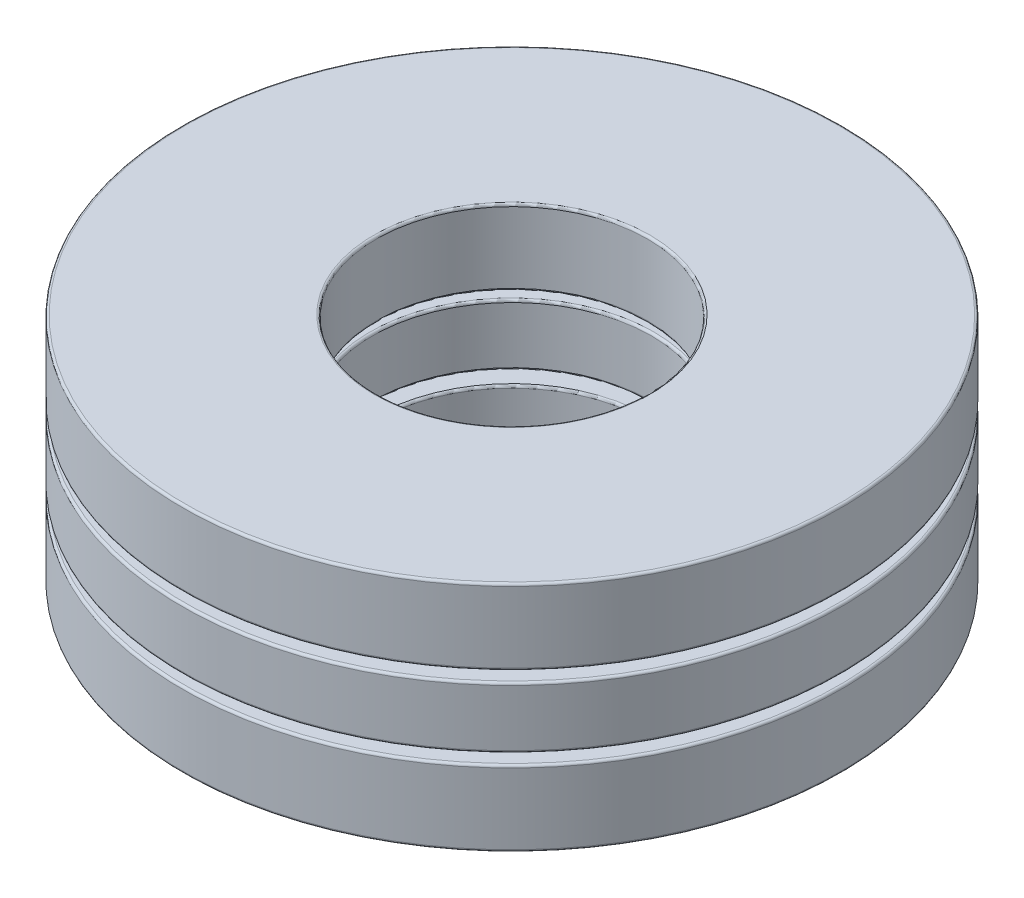
SolidWorks part; units mm, degrees
ref_plane "Front Plane" through (0, 0, 0) normal (0, 0, 1) x (1, 0, 0)
ref_plane "Top Plane" through (0, 0, 0) normal (0, 1, 0) x (1, 0, 0)
ref_plane "Right Plane" through (0, 0, 0) normal (1, 0, 0) x (0, 0, -1)
sketch "Sketch1" plane through (0, 0, 0) normal (0, 0, 1) x (1, 0, 0)
  line L0 (-8.5, 0.7275) -> (-8.5, -0.7275)
  line L1 (-8.44, -0.7875) -> (-3.66, -0.7875)
  line L2 (-3.6, -0.7275) -> (-3.6, 0.7275)
  line L3 (-3.66, 0.7875) -> (-8.44, 0.7875)
  line L4 (0, -3) -> (0, 3) construction
  line L5 (-8.5, 2.94) -> (-8.5, 1.115)
  line L6 (-8.44, 1.055) -> (-3.56, 1.055)
  line L7 (-3.5, 1.115) -> (-3.5, 2.94)
  line L8 (-3.56, 3) -> (-8.44, 3)
  line L9 (-6.375, 1.3225) -> (-6.375, 0.7875) construction
  arc A0 (-8.5, 0.7275) -> (-8.44, 0.7875) centre (-8.44, 0.7275) cw
  arc A1 (-3.66, 0.7875) -> (-3.6, 0.7275) centre (-3.66, 0.7275) cw
  arc A2 (-3.6, -0.7275) -> (-3.66, -0.7875) centre (-3.66, -0.7275) cw
  arc A3 (-8.44, -0.7875) -> (-8.5, -0.7275) centre (-8.44, -0.7275) cw
  circle A4 centre (-6.375, 0) radius 1.26
  arc A5 (-3.56, 1.055) -> (-3.5, 1.115) centre (-3.56, 1.115) ccw
  arc A6 (-3.5, 2.94) -> (-3.56, 3) centre (-3.56, 2.94) ccw
  arc A7 (-8.44, 3) -> (-8.5, 2.94) centre (-8.44, 2.94) ccw
  arc A8 (-8.5, 1.115) -> (-8.44, 1.055) centre (-8.44, 1.115) ccw
  circle A9 centre (-6.375, 0) radius 1.3225 construction
  point P15 (-3.6, 0)
  point P24 (-6.375, 1.055)
  dimension "D1" = 0.06
  dimension "Thickness" = 6
  dimension "D2" = 1.575
  dimension "D3" = 0.0625
  dimension "Washer ID" = 7
sketch "Sketch2" plane through (0, 0, 0) normal (0, 0, 1) x (1, 0, 0)
  line L0 (-3.6, -0.7275) -> (-3.6, 0.7275) construction
  line L1 (-8.44, -0.7875) -> (-3.66, -0.7875) construction
  line L2 (-8.5, 0.7275) -> (-8.5, -0.7275) construction
  line L3 (-3.66, 0.7875) -> (-8.44, 0.7875) construction
  line L4 (-3.6, -0.7275) -> (-3.6, 0.7275)
  line L5 (-8.44, -0.7875) -> (-3.66, -0.7875)
  line L6 (-8.5, 0.7275) -> (-8.5, -0.7275)
  line L7 (-3.66, 0.7875) -> (-8.44, 0.7875)
  arc A0 (-3.6, 0.7275) -> (-3.66, 0.7875) centre (-3.66, 0.7275) ccw construction
  arc A1 (-3.66, -0.7875) -> (-3.6, -0.7275) centre (-3.66, -0.7275) ccw construction
  arc A2 (-8.5, -0.7275) -> (-8.44, -0.7875) centre (-8.44, -0.7275) ccw construction
  arc A3 (-8.44, 0.7875) -> (-8.5, 0.7275) centre (-8.44, 0.7275) ccw construction
  arc A4 (-3.6, 0.7275) -> (-3.66, 0.7875) centre (-3.66, 0.7275) ccw
  arc A5 (-3.66, -0.7875) -> (-3.6, -0.7275) centre (-3.66, -0.7275) ccw
  arc A6 (-8.5, -0.7275) -> (-8.44, -0.7875) centre (-8.44, -0.7275) ccw
  arc A7 (-8.44, 0.7875) -> (-8.5, 0.7275) centre (-8.44, 0.7275) ccw
revolve "Revolve2" add sketch "Sketch2" angle 360 about L4
sketch "Sketch4" plane through (0, 0, 0) normal (0, 0, 1) x (1, 0, 0)
  line L0 (-3, 0) -> (3, 0) construction
  line L1 (0, -3) -> (0, 3) construction
  line L2 (-3.5, 1.115) -> (-3.5, 2.94) construction
  line L3 (-8.5, 2.94) -> (-8.5, 1.115) construction
  line L5 (-8.44, 1.055) -> (-7.1725, 1.055)
  line L6 (-8.5, 2.94) -> (-8.5, 1.115)
  line L10 (-7.1725, 1.055) -> (-5.5775, 1.055) construction
  line L11 (-6.375, 1.3225) -> (-6.375, 1.055) construction
  line L12 (-6.375, 1.3225) -> (-6.375, 1.055) construction
  line L13 (-6.375, 1.3225) -> (-6.375, 0.7875) construction
  line L14 (-3.5, 1.115) -> (-3.5, 2.94)
  line L15 (-3.56, 3) -> (-8.44, 3) construction
  line L16 (-3.56, 3) -> (-8.44, 3)
  line L17 (-5.5775, 1.055) -> (-3.56, 1.055)
  arc A0 (-5.5775, 1.055) -> (-7.1725, 1.055) centre (-6.375, 0) ccw
  arc A1 (-3.56, 1.055) -> (-3.5, 1.115) centre (-3.56, 1.115) ccw construction
  circle A2 centre (-6.375, 0) radius 1.3225 construction
  arc A3 (-3.56, 1.055) -> (-3.5, 1.115) centre (-3.56, 1.115) ccw
  arc A4 (-3.5, 2.94) -> (-3.56, 3) centre (-3.56, 2.94) ccw construction
  arc A8 (-8.5, 1.115) -> (-8.44, 1.055) centre (-8.44, 1.115) ccw
  arc A10 (-3.5, 2.94) -> (-3.56, 3) centre (-3.56, 2.94) ccw
  arc A11 (-8.44, 3) -> (-8.5, 2.94) centre (-8.44, 2.94) ccw construction
  arc A12 (-8.44, 3) -> (-8.5, 2.94) centre (-8.44, 2.94) ccw
revolve "Revolve3" add sketch "Sketch4" angle 360 about L4
mirror "Mirror1" about plane through (0, 0, 0) normal (0, 1, 0) of bodies 107
sketch "Sketch3" plane through (0, 0, 0) normal (0, 0, 1) x (1, 0, 0)
  line L0 (-6.375, 1.3225) -> (-6.375, -1.3225)
  arc A0 (-6.375, 1.3225) -> (-6.375, -1.3225) centre (-6.375, 0) ccw
revolve "Cut-Revolve1" cut sketch "Sketch3" angle 360 about L0
sketch "Sketch5" plane through (0, 0, 0) normal (0, 0, 1) x (1, 0, 0)
  line L0 (-6.375, 1.26) -> (-6.375, -1.26)
  arc A0 (-6.375, 1.26) -> (-6.375, -1.26) centre (-6.375, 0) ccw
  circle A1 centre (-6.375, 0) radius 1.26 construction
revolve "Revolve4" add sketch "Sketch5" angle 360 about L0
pattern_circular "CirPattern2" count 4 over 360 about axis through (0, -3, 0) along (0, 1, 0) of "Cut-Revolve1" reverse direction yes
pattern_circular "CirPattern3" count 4 over 360 about axis through (0, -3, 0) along (0, 1, 0) reverse direction yes of bodies 109
sketch "Sketch6" plane through (0, 0, 0) normal (0, 1, 0) x (1, 0, 0)
  circle A0 centre (0, 0) radius 8.5
  circle A1 centre (0, 0) radius 3.5
  dimension "Washer ID" = 7
  dimension "OD" = 17
ref_plane "Contact Plane 1" through (0, 3, 0) normal (0, 1, 0) x (1, 0, 0)
ref_plane "Contact Plane 2" through (0, -3, 0) normal (0, -1, 0) x (-1, 0, 0)
ref_axis "Center Axis 1" through (0, 0.7275, 0) along (0, -1, 0)
equation "\"D2@Sketch1\"=\"Ball Diameter@Sketch1\"*.625"
equation "\"D1@Sketch1\"=\"Thickness@Sketch1\"*.01"
equation "\"D1@CirPattern3\" = \"Balls@CirPattern2\""
